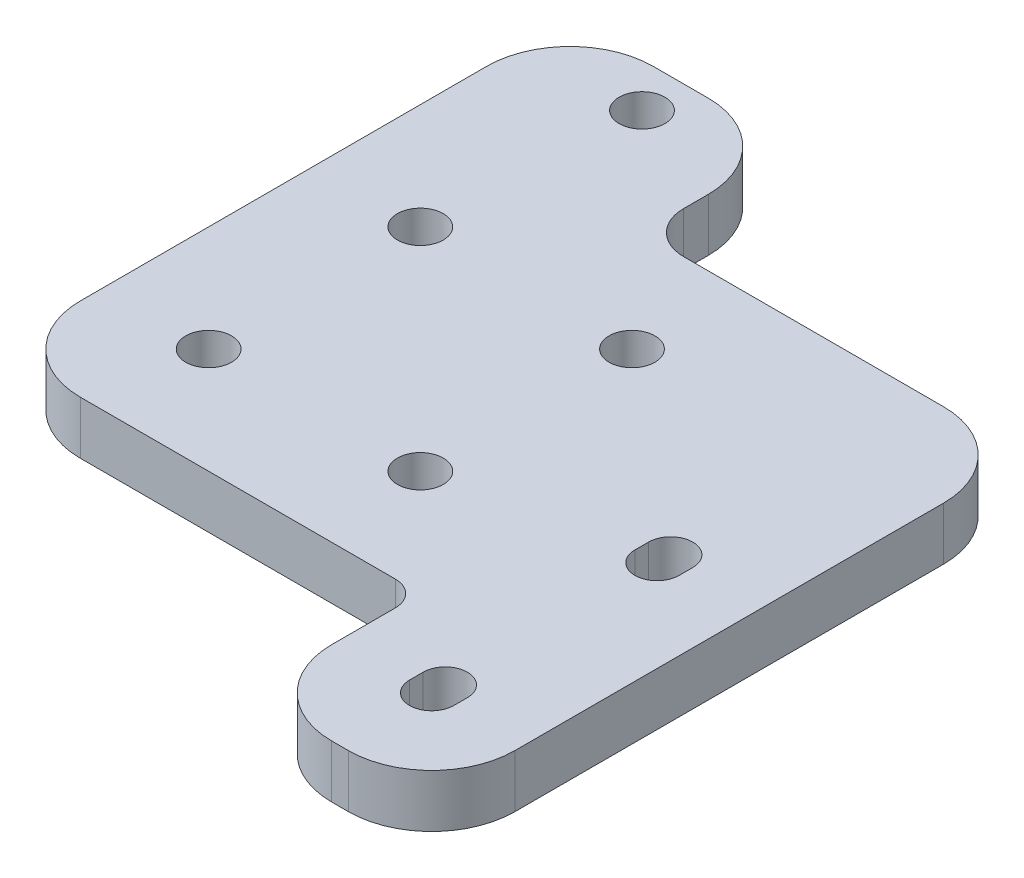
SolidWorks part; units mm, degrees
ref_plane "Front" through (0, 0, 0) normal (0, 0, 1) x (1, 0, 0)
ref_plane "Top" through (0, 0, 0) normal (0, 1, 0) x (1, 0, 0)
ref_plane "Right" through (0, 0, 0) normal (1, 0, 0) x (0, 0, -1)
sketch "Sketch1" plane through (0, 0, 0) normal (0, 1, 0) x (1, 0, 0)
  line L0 (0, 0) -> (47.4, 0) construction
  line L1 (25.4, -25.4) -> (-25.4, -25.4)
  line L2 (25.4, -25.4) -> (25.4, 25.4) construction
  line L3 (25.4, 25.4) -> (-25.4, 25.4) construction
  line L4 (-25.4, -25.4) -> (-25.4, 25.4)
  line L5 (25.4, -25.4) -> (-25.4, 25.4) construction
  line L6 (25.4, 25.4) -> (-25.4, -25.4) construction
  line L7 (1.2, 25.4) -> (1.2, 76.2) construction
  line L8 (-12.7, 25.4) -> (-12.7, -25.4) construction
  line L9 (12.7, -25.4) -> (12.7, 25.4) construction
  line L10 (0, 0) -> (-25.4, 0) construction
  line L11 (-12.7, 0) -> (-12.7, 25.4) construction
  line L12 (-12.7, 12.7) -> (12.7, 12.7) construction
  line L13 (5.5675, -41.4) -> (47.4, -41.4) construction
  line L14 (25.4, -25.4) -> (25.4, -46.04)
  line L15 (25.4, -46.04) -> (36.4, -46.04)
  line L17 (36.4, -33.4) -> (36.4, 25.4) construction
  line L18 (36.4, -8) -> (36.4, -6.36) construction
  line L26 (47.4, -41.4) -> (47.4, 0) construction
  line L30 (47.4, 0) -> (0, 0) construction
  line L31 (1.2, 76.2) -> (-49.6, 76.2) construction
  line L32 (36.4, -46.04) -> (47.4, -46.04)
  line L33 (47.4, -46.04) -> (47.4, 25.4)
  line L34 (47.4, 25.4) -> (25.4, 25.4)
  line L36 (36.4, -35.04) -> (36.4, -33.4) construction
  line L37 (36.4, -35.04) -> (36.4, -46.04) construction
  line L38 (-49.6, 76.2) -> (-49.6, 25.4) construction
  line L39 (-49.6, -25.4) -> (-25.4, -25.4) construction
  line L40 (-49.6, 25.4) -> (-25.4, 25.4) construction
  line L41 (-11.5, 25.4) -> (-11.5, 76.2) construction
  line L42 (-25.4, 25.4) -> (-25.4, 43.35)
  line L43 (-25.4, 43.35) -> (1.2, 43.35)
  line L44 (1.2, 43.35) -> (1.2, 25.4)
  line L45 (1.2, 25.4) -> (25.4, 25.4)
  circle A0 centre (-12.7, 12.7) radius 2.5 construction
  circle A1 centre (12.7, 12.7) radius 2.5 construction
  circle A2 centre (-12.7, -12.7) radius 2.5 construction
  circle A3 centre (12.7, -12.7) radius 2.5 construction
  circle A4 centre (36.4, -6.36) radius 6.36 construction
  circle A5 centre (36.4, -8) radius 8 construction
  circle A6 centre (-11.5, 38.1) radius 5.25 construction
  circle A10 centre (36.4, -35.04) radius 6.36 construction
  circle A11 centre (36.4, -35.04) radius 11 construction
  circle A15 centre (-11.5, 38.1) radius 2.5 construction
  circle A20 centre (36.4, -35.04) radius 2.5 construction
  circle A25 centre (36.4, -33.4) radius 8 construction
  circle A26 centre (36.4, -33.4) radius 11 construction
  point P0 (0, 0)
  dimension "D6" = 5
  dimension "D7" = 22
  dimension "D9" = 16
  dimension "D11" = 10.5
  dimension "D12" = 16
  dimension "D16" = 12.7
  dimension "D8" = 12.72
  dimension "D10" = 5
  dimension "D1" = 50.8
  dimension "D2" = 50.8
  dimension "D3" = 50.8
  dimension "D4" = 12.7
  dimension "D5" = 25.4
  dimension "D14" = 50.8
  dimension "D15" = 24.2
  dimension "D22" = 12.7
extrude "Boss-Extrude1" add sketch "Sketch1" along normal blind 6.35
hole_wizard "M5 Clearance Hole1" positions "Sketch3" profile "Sketch2" hole size "M5" standard "ISO" end condition through all
sketch "Sketch3" plane through (0, 6.35, 0) normal (0, 1, 0) x (1, 0, 0)
  point P0 (-12.7, 12.7)
  point P3 (12.7, 12.7)
  point P6 (12.7, -12.7)
  point P9 (-12.7, -12.7)
  point P15 (-11.5, 38.1)
sketch "Sketch2" plane through (-12.7, 6.35, -12.7) normal (1, 0, 0) x (0, 0, 1)
  line L0 (0, 0) -> (0, 6.35)
  line L1 (0, 6.35) -> (2.75, 6.35)
  line L2 (2.75, 6.35) -> (2.75, 0)
  line L5 (2.75, 0) -> (0, 0)
  line L11 (0, -6.35) -> (0, 107.95) construction
  dimension "Thru Hole Dia." = 5.5
  dimension "Thru Hole Depth" = 6.35
sketch "Sketch7" plane through (0, 6.35, 0) normal (0, 1, 0) x (1, 0, 0)
  line L0 (36.4, -6.36) -> (36.4, -8) construction
  line L1 (36.4, -33.4) -> (36.4, -35.04) construction
  line L2 (33.75, -33.4) -> (33.75, -35.04)
  line L3 (33.75, -6.36) -> (33.75, -8)
  line L4 (39.05, -33.4) -> (39.05, -35.04)
  line L5 (39.05, -6.36) -> (39.05, -8)
  arc A0 (33.75, -33.4) -> (39.05, -33.4) centre (36.4, -33.4) cw
  arc A1 (33.75, -35.04) -> (39.05, -35.04) centre (36.4, -35.04) ccw
  arc A2 (33.75, -6.36) -> (39.05, -6.36) centre (36.4, -6.36) cw
  arc A3 (33.75, -8) -> (39.05, -8) centre (36.4, -8) ccw
  dimension "D1" = 2.65
  dimension "D2" = 2.65
extrude "Cut-Extrude2" cut sketch "Sketch7" against normal through all
fillet "Fillet1" radius 10 6 edges at (47.4, 3.175, 46.04) (47.4, 3.175, -25.4) (-25.4, 3.175, 25.4) (-25.4, 3.175, -43.35) (1.2, 3.175, -43.35) (25.4, 3.175, 46.04)
fillet "Fillet2" radius 3 1 edges at (25.4, 3.175, 25.4)
fillet "Fillet3" radius 5 1 edges at (1.2, 3.175, -25.4)
